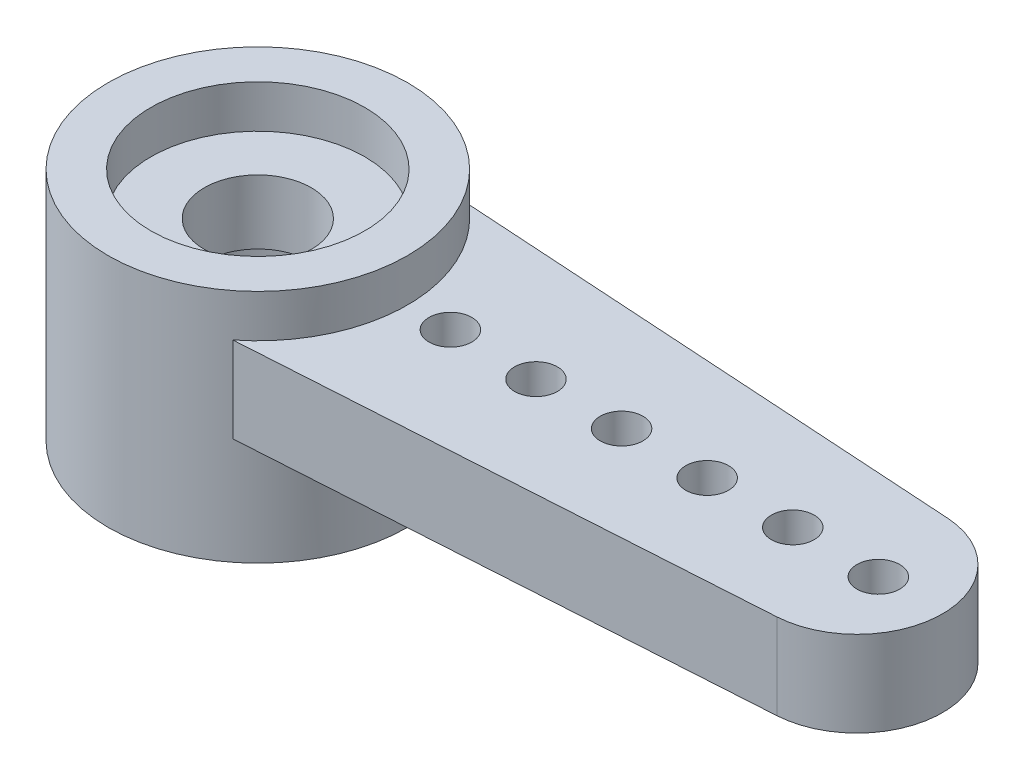
SolidWorks part; units mm, degrees
ref_plane "Front Plane" through (0, 0, 0) normal (0, 0, 1) x (1, 0, 0)
ref_plane "Top Plane" through (0, 0, 0) normal (0, 1, 0) x (1, 0, 0)
ref_plane "Right Plane" through (0, 0, 0) normal (1, 0, 0) x (0, 0, -1)
sketch "Sketch1" plane through (0, 0, 0) normal (0, 1, 0) x (1, 0, 0)
  circle A0 centre (0, 0) radius 3.5
  dimension "D1" = 7
extrude "Boss-Extrude1" add sketch "Sketch1" along normal blind 5.5
sketch "Sketch2" plane through (0, 5.5, 0) normal (0, 1, 0) x (1, 0, 0)
  circle A0 centre (0, 0) radius 2.5
  dimension "D1" = 5
extrude "Cut-Extrude1" cut sketch "Sketch2" against normal blind 1
sketch "Sketch3" plane through (0, 0, 0) normal (0, -1, 0) x (1, 0, 0)
  circle A0 centre (0, 0) radius 2.5
  dimension "D1" = 5
extrude "Cut-Extrude2" cut sketch "Sketch3" against normal blind 3
sketch "Sketch4" plane through (0, 4.5, 0) normal (0, 1, 0) x (1, 0, 0)
  circle A0 centre (0, 0) radius 1.25
  dimension "D1" = 2.5
extrude "Cut-Extrude3" cut sketch "Sketch4" against normal through all
sketch "Sketch5" plane through (0, 4.5, 0) normal (0, 1, 0) x (1, 0, 0)
  line L0 (2.1651, 2.75) -> (14.1258, 1.996)
  line L1 (2.1651, -2.75) -> (14.1258, -1.996)
  circle A0 centre (0, 0) radius 3.5 construction
  arc A1 (2.1651, -2.75) -> (2.1651, 2.75) centre (0, 0) ccw
  arc A2 (14.1258, -1.996) -> (14.1258, 1.996) centre (14, 0) ccw
  dimension "D1" = 19.5
  dimension "D3" = 2
  dimension "D2" = 5.5
extrude "Boss-Extrude2" add sketch "Sketch5" against normal blind 2
sketch "Sketch6" plane through (0, 4.5, 0) normal (0, 1, 0) x (1, 0, 0)
  line L0 (4.5, 0) -> (6.5, 0) construction
  line L1 (6.5, 0) -> (8.5, 0) construction
  line L2 (8.5, 0) -> (10.5, 0) construction
  line L3 (10.5, 0) -> (12.5, 0) construction
  line L4 (12.5, 0) -> (14.5, 0) construction
  line L5 (0, 0) -> (4.5, 0) construction
  arc A1 (14.1258, -1.996) -> (14.1258, 1.996) centre (14, 0) ccw construction
  circle A2 centre (4.5, 0) radius 0.5
  circle A3 centre (6.5, 0) radius 0.5
  circle A4 centre (8.5, 0) radius 0.5
  circle A5 centre (10.5, 0) radius 0.5
  circle A6 centre (12.5, 0) radius 0.5
  circle A7 centre (14.5, 0) radius 0.5
  dimension "D3" = 1
  dimension "D1" = 10
  dimension "D2" = 1.5
extrude "Cut-Extrude4" cut sketch "Sketch6" against normal through all
